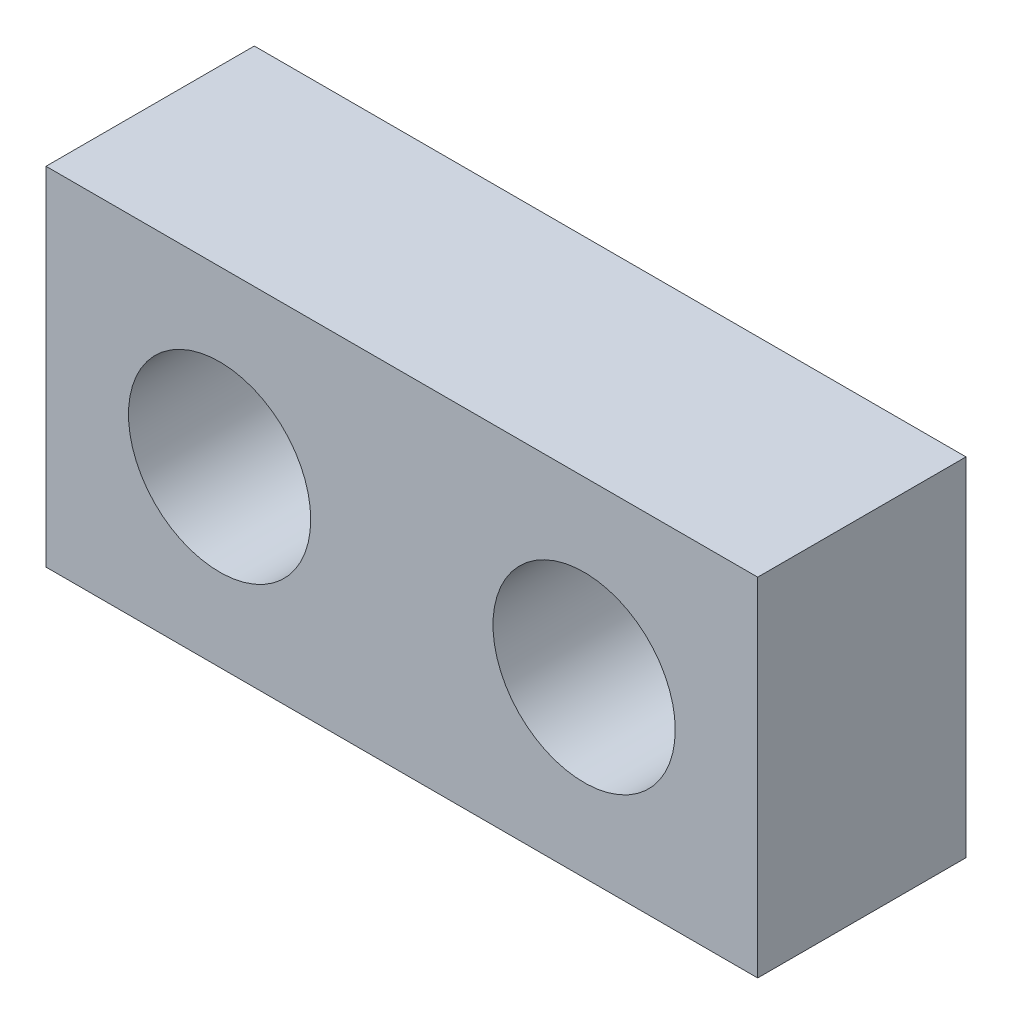
SolidWorks part; units mm, degrees
ref_plane "xy_plane" through (0, 0, 0) normal (0, 0, 1) x (1, 0, 0)
ref_plane "zx_plane" through (0, 0, 0) normal (0, 1, 0) x (1, 0, 0)
ref_plane "yz_plane" through (0, 0, 0) normal (1, 0, 0) x (0, 0, -1)
ref_axis "x_axis" through (-80.9, 0, 0) along (1, 0, 0)
ref_axis "y_axis" through (0, -50, 0) along (0, 1, 0)
ref_axis "z_axis" through (0, 0, -80.9) along (0, 0, 1)
ref_plane "xMid_plane" through (0, 0, 0) normal (1, 0, 0) x (0, 0, -1)
ref_plane "xMin_plane" through (-10.25, 0, 0) normal (1, 0, 0) x (0, 0, -1)
ref_plane "xMax_plane" through (10.25, 0, 0) normal (1, 0, 0) x (0, 0, -1)
ref_plane "yMid_plane" through (0, 0, 0) normal (0, 1, 0) x (1, 0, 0)
ref_plane "yMin_plane" through (0, -5, 0) normal (0, 1, 0) x (1, 0, 0)
ref_plane "yMax_plane" through (0, 5, 0) normal (0, 1, 0) x (1, 0, 0)
ref_plane "zMid_plane" through (0, 0, 0) normal (0, 0, 1) x (1, 0, 0)
ref_plane "zMin_plane" through (0, 0, -3) normal (0, 0, 1) x (1, 0, 0)
ref_plane "zMax_plane" through (0, 0, 3) normal (0, 0, 1) x (1, 0, 0)
sketch "projectionXy_sketch" plane through (0, 0, 0) normal (0, 0, 1) x (1, 0, 0)
  line L0 (7.9674, 5) -> (-7.9674, 5) construction
  line L1 (-10.25, 5) -> (10.25, 5)
  line L2 (-10.25, 5) -> (-10.25, -5)
  line L3 (-10.25, -5) -> (10.25, -5)
  line L4 (10.25, 5) -> (10.25, -5)
  line L5 (8.8464, -5) -> (-8.8464, -5) construction
  line L6 (10.25, -4.5754) -> (10.25, 4.5754) construction
  line L7 (-10.25, -6.6038) -> (-10.25, 6.6038) construction
extrude "mainBody_extrude" add sketch "projectionXy_sketch" along normal up to surface (3 mm away) from surface up to plane "zMax_plane" starting at plane "zMin_plane"
sketch "viseScrewClearanceHoles_sketch" plane through (0, 0, 0) normal (0, 0, 1) x (1, 0, 0)
  line L0 (-5.25, 0) -> (5.25, 0) construction
  line L1 (0, -5.7783) -> (0, 5.7783) construction
  line L3 (9.2439, 0) -> (-9.2439, 0) construction
  circle A0 centre (-5.25, 0) radius 2.625
  circle A1 centre (5.25, 0) radius 2.625
  point P0 (0, 0)
  dimension "D1" = 5.25
  dimension "D2" = 10.5
extrude "viseScrewClearanceHoles_cut" cut sketch "viseScrewClearanceHoles_sketch" against normal through all both and the other way through all from surface starting at plane "zMid_plane"
equation "\"D1@xMin_plane\" = \"externalParameters.this.extent.x\" / 2"
equation "\"D1@xMax_plane\" = \"externalParameters.this.extent.x\" / 2"
equation "\"D1@yMin_plane\" = \"externalParameters.this.extent.y\" / 2"
equation "\"D1@yMax_plane\" = \"externalParameters.this.extent.y\" / 2"
equation "\"D1@zMin_plane\"= \"externalParameters.this.extent.z\" / 2"
equation "\"D1@zMax_plane\" = \"externalParameters.this.extent.z\" / 2"
equation "\"D1@viseScrewClearanceHoles_sketch\" = \"externalParameters.arm.viseScrew.closeFitDiameter\""
equation "\"D2@viseScrewClearanceHoles_sketch\" = \"externalParameters.arm.viseScrews.intervalX\""
